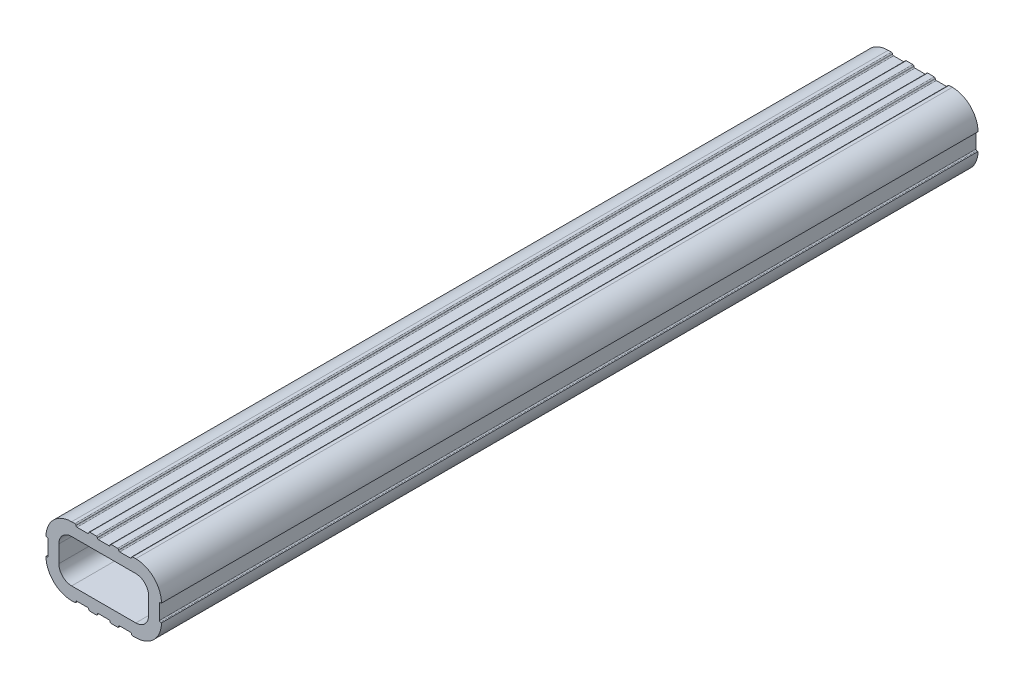
SolidWorks part; units mm, degrees
material "Silicon Rubber"
ref_plane "Front Plane" through (0, 0, 0) normal (0, 0, 1) x (1, 0, 0)
ref_plane "Top Plane" through (0, 0, 0) normal (0, 1, 0) x (1, 0, 0)
ref_plane "Right Plane" through (0, 0, 0) normal (1, 0, 0) x (0, 0, -1)
sketch "Sketch1" plane through (0, 0, 0) normal (0, 0, 1) x (1, 0, 0)
  line L0 (0, 3) -> (-15, 3)
  line L1 (-21, -3) -> (-21, -7)
  line L2 (0, -13) -> (-15, -13)
  line L3 (6, -3) -> (6, -7)
  line L5 (0, 0) -> (-15, 0)
  line L6 (3, -3) -> (3, -7)
  line L7 (0, -10) -> (-15, -10)
  line L8 (-18, -3) -> (-18, -7)
  arc A0 (-15, -10) -> (-18, -7) centre (-15, -7) cw
  arc A1 (3, -7) -> (0, -10) centre (0, -7) cw
  arc A2 (0, 0) -> (3, -3) centre (0, -3) cw
  arc A3 (-15, 0) -> (-18, -3) centre (-15, -3) ccw
  arc A4 (-15, 3) -> (-21, -3) centre (-15, -3) ccw
  arc A5 (-15, -13) -> (-21, -7) centre (-15, -7) cw
  arc A6 (6, -7) -> (0, -13) centre (0, -7) cw
  arc A7 (0, 3) -> (6, -3) centre (0, -3) cw
  point P11 (-18, -10)
  point P16 (3, 0)
  point P19 (-18, 0)
  dimension "D7" = 3
  dimension "D1" = 10
  dimension "D2" = 21
  dimension "D3" = 3
extrude "Boss-Extrude1" add sketch "Sketch1" along normal blind 191
sketch "Sketch2" plane through (0, 0, 191) normal (0, 0, 1) x (1, 0, 0)
  line L0 (0, 3) -> (-15, 3) construction
  line L5 (-9, 3.5) -> (-6, 3.5)
  line L6 (-9, 3.5) -> (-9, 2.5)
  line L7 (-9, 2.5) -> (-6, 2.5)
  line L8 (-6, 3.5) -> (-6, 2.5)
  line L9 (-7.5, 3) -> (-7.5, -13) construction
  line L10 (-15, -13) -> (0, -13) construction
  line L11 (-21, -5) -> (6, -5) construction
  line L12 (-21, -3) -> (-21, -7) construction
  line L13 (6, -7) -> (6, -3) construction
  line L14 (-14, 3.5) -> (-11, 3.5)
  line L15 (-14, 3.5) -> (-14, 2.5)
  line L16 (-14, 2.5) -> (-11, 2.5)
  line L17 (-11, 3.5) -> (-11, 2.5)
  line L18 (-4, 3.5) -> (-1, 3.5)
  line L19 (-4, 3.5) -> (-4, 2.5)
  line L20 (-4, 2.5) -> (-1, 2.5)
  line L21 (-1, 3.5) -> (-1, 2.5)
  line L22 (-1, -13.5) -> (-1, -12.5)
  line L23 (-4, -12.5) -> (-1, -12.5)
  line L24 (-4, -13.5) -> (-4, -12.5)
  line L25 (-4, -13.5) -> (-1, -13.5)
  line L26 (-11, -13.5) -> (-11, -12.5)
  line L27 (-14, -12.5) -> (-11, -12.5)
  line L28 (-14, -13.5) -> (-14, -12.5)
  line L29 (-14, -13.5) -> (-11, -13.5)
  line L30 (-6, -13.5) -> (-6, -12.5)
  line L31 (-9, -12.5) -> (-6, -12.5)
  line L32 (-9, -13.5) -> (-9, -12.5)
  line L33 (-9, -13.5) -> (-6, -13.5)
  line L34 (5.5, -7) -> (5.5, -3)
  line L35 (-21.5, -7) -> (-20.5, -7)
  line L36 (-21.5, -7) -> (-21.5, -3)
  line L37 (-21.5, -3) -> (-20.5, -3)
  line L38 (-20.5, -7) -> (-20.5, -3)
  line L39 (6.5, -3) -> (5.5, -3)
  line L40 (6.5, -7) -> (6.5, -3)
  line L41 (6.5, -7) -> (5.5, -7)
  point P7 (-7.5, 2.5)
  point P41 (-20.5, -5)
  dimension "D1" = 0.5
  dimension "D2" = 3
  dimension "D5" = 4
  dimension "D6" = 0.5
  dimension "D7" = 1
  dimension "D8" = 1
  dimension "D3" = 2
  dimension "D4" = 2
extrude "Cut-Extrude1" cut sketch "Sketch2" against normal through all
fillet "Fillet1" radius 0.25 28 edges at (-20.5, -7, 95.5) (-20.5, -3, 95.5) (-14, -13, 95.5) (-11, -12.5, 95.5) (-6, -12.5, 95.5) (-11, -13, 95.5) (-9, -13, 95.5) (-6, -13, 95.5) (-4, -13, 95.5) (-14, -12.5, 95.5) (-9, -12.5, 95.5) (-1, -13, 95.5) (-1, -12.5, 95.5) (5.5, -7, 95.5) (-4, -12.5, 95.5) (5.5, -3, 95.5) (-1, 3, 95.5) (-4, 3, 95.5) (-6, 3, 95.5) (-14, 3, 95.5) (-11, 3, 95.5) (-9, 3, 95.5) (-1, 2.5, 95.5) (-4, 2.5, 95.5) (-6, 2.5, 95.5) (-9, 2.5, 95.5) (-11, 2.5, 95.5) (-14, 2.5, 95.5)
